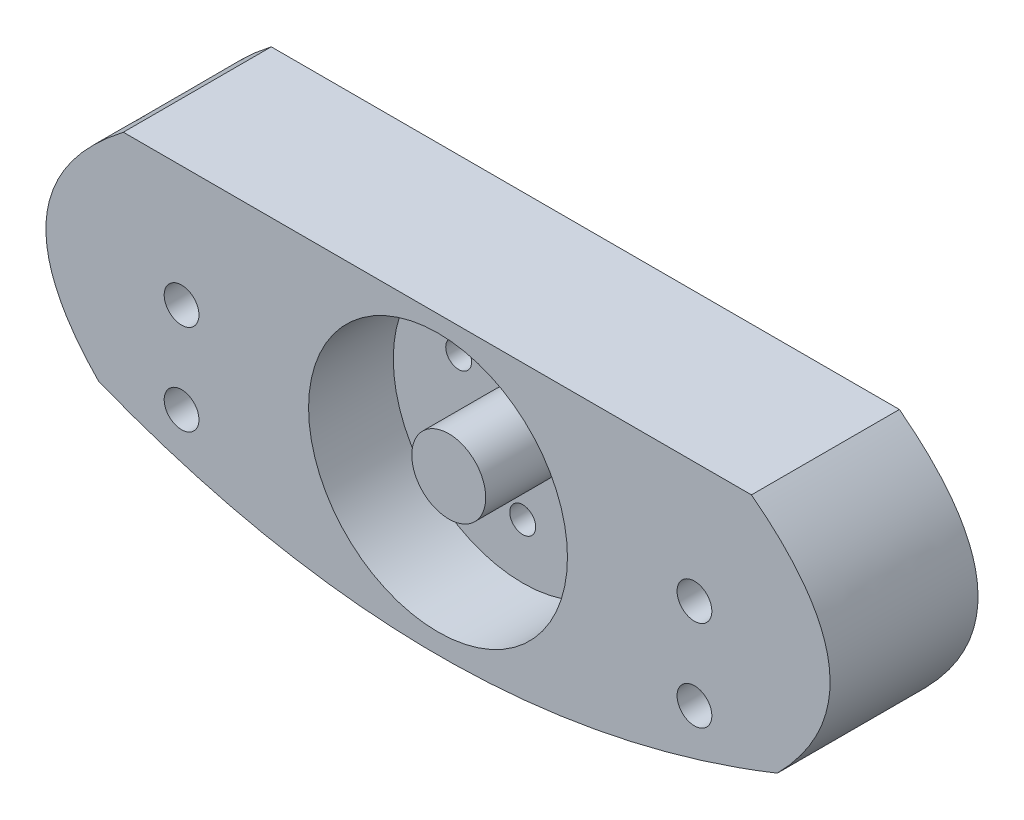
SolidWorks part; units mm, degrees
ref_plane "Front Plane" through (0, 0, 0) normal (0, 0, 1) x (1, 0, 0)
ref_plane "Top Plane" through (0, 0, 0) normal (0, 1, 0) x (1, 0, 0)
ref_plane "Right Plane" through (0, 0, 0) normal (1, 0, 0) x (0, 0, -1)
sketch "Sketch2" plane through (0, 0, 0) normal (0, 0, 1) x (1, 0, 0)
  line L1 (42.3768, 8.6832) -> (-42.5401, 8.6832)
  line L2 (42.3768, 8.6832) -> (-42.5401, 8.6832)
  parabola Q3 (45.8737, -22.1555) -> (42.3768, 8.6832) focus (46.195, -7.6248) apex (52.9944, -7.3425)
  parabola Q4 (-42.5401, 8.6832) -> (-45.8737, -22.1555) focus (-46.1445, -7.62) apex (-52.997, -7.3593)
  parabola Q5 (-45.8737, -22.1555) -> (45.8737, -22.1555) focus (0.744, 26.3908) apex (1.3864, -31.2701)
  parabola Q6 (45.8737, -22.1555) -> (42.3768, 8.6832) focus (46.195, -7.6248) apex (52.9944, -7.3425)
  parabola Q7 (-42.5401, 8.6832) -> (-45.8737, -22.1555) focus (-46.1445, -7.62) apex (-52.997, -7.3593)
  parabola Q8 (-45.8737, -22.1555) -> (45.8737, -22.1555) focus (0.744, 26.3908) apex (1.3864, -31.2701)
  dimension "D1" = 0
extrude "Boss-Extrude1" add sketch "Sketch2" along normal blind 20
sketch "Sketch4" plane through (0, 0, 20) normal (0, 0, 1) x (1, 0, 0)
  line L1 (0, -17) -> (0, -2) construction
  circle A1 centre (0, -11.063) radius 17.5
  point P5 (0, -11.063)
  dimension "D1" = 35
extrude "Cut-Extrude1" cut sketch "Sketch4" against normal blind 11.4533
sketch "Sketch5" plane through (0, 0, 8.5467) normal (0, 0, 1) x (1, 0, 0)
  line L0 (0, -17) -> (0, -2) construction
  circle A1 centre (0, -11.063) radius 5
  circle A2 centre (0, -11.063) radius 17.5 construction
  dimension "D1" = 10
extrude "Boss-Extrude2" add sketch "Sketch5" along normal blind 10
sketch "Sketch6" plane through (0, 0, 8.5467) normal (0, 0, 1) x (1, 0, 0)
  line L0 (0, -17) -> (0, -2) construction
  line L1 (0, -21.1295) -> (8.6603, -6.1295)
  line L2 (8.6603, -6.1295) -> (-8.6603, -6.1295)
  line L3 (-8.6603, -6.1295) -> (0, -21.1295)
  circle A0 centre (0, -11.1295) radius 10
  point P6 (0, 0)
  dimension "D1" = 20
hole_wizard "CBORE for M5 Hex Head Machine Screw2" positions "Sketch9" profile "Sketch10" counterbore size "M5" standard "ANSI Metric"
sketch "Sketch9" plane through (0, 0, 0) normal (0, 0, -1) x (-1, 0, 0)
  point P0 (-8.6603, -6.1295)
  point P3 (0, -21.1295)
  point P6 (8.6603, -6.1295)
sketch "Sketch10" plane through (8.6603, -6.1295, 0) normal (1, 0, 0) x (0, 1, 0)
  line L0 (0, 0) -> (0, 12.75)
  line L1 (0, 12.75) -> (1.75, 11)
  line L2 (1.75, 11) -> (1.75, 4)
  line L3 (1.75, 4) -> (3.5, 4)
  line L4 (3.5, 4) -> (3.5, 0)
  line L5 (3.5, 0) -> (0, 0)
  line L10 (0, 12.75) -> (-1.75, 11) construction
  line L11 (0, -6.35) -> (0, 107.95) construction
  dimension "Hole Dia." = 3.5
  dimension "Hole Depth" = 11
  dimension "C'Bore Dia." = 7
  dimension "C'Bore Depth" = 4
  dimension "Drill Angle" = 90
sketch "Sketch11" plane through (0, 0, 20) normal (0, 0, 1) x (1, 0, 0)
  circle A0 centre (-34.6698, -19.8652) radius 2.35 construction
  circle A1 centre (-34.6698, -7.6169) radius 2.35 construction
  circle A2 centre (34.6698, -7.6169) radius 2.35 construction
  circle A3 centre (34.6698, -19.8652) radius 2.35 construction
  circle A4 centre (-34.6698, -19.8652) radius 2.35
  circle A5 centre (-34.6698, -7.6169) radius 2.35
  circle A6 centre (34.6698, -7.6169) radius 2.35
  circle A7 centre (34.6698, -19.8652) radius 2.35
extrude "Cut-Extrude2" cut sketch "Sketch11" against normal through all both and the other way through all
